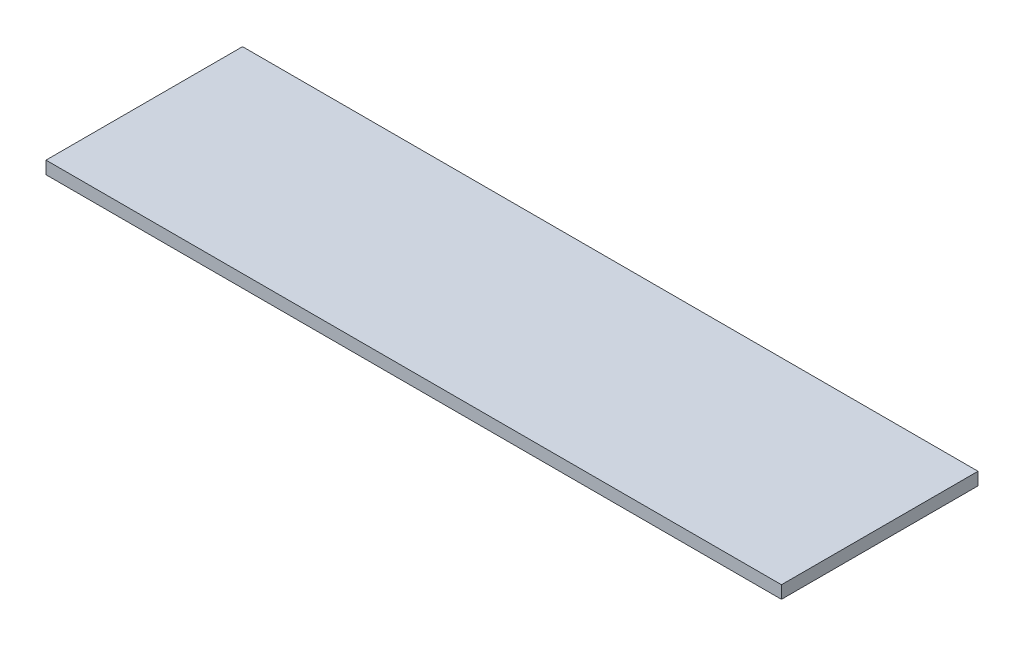
SolidWorks part; units mm, degrees
ref_plane "Plan de face" through (0, 0, 0) normal (0, 0, 1) x (1, 0, 0)
ref_plane "Plan de dessus" through (0, 0, 0) normal (0, 1, 0) x (1, 0, 0)
ref_plane "Plan de droite" through (0, 0, 0) normal (1, 0, 0) x (0, 0, -1)
sketch "Esquisse1" plane through (0, 0, 0) normal (0, 1, 0) x (1, 0, 0)
  line L1 (0, 0) -> (580, 0)
  line L2 (0, 0) -> (0, 155)
  line L3 (0, 155) -> (580, 155)
  line L4 (580, 0) -> (580, 155)
  dimension "D1" = 580
  dimension "D2" = 155
extrude "Boss.-Extru.1" add sketch "Esquisse1" along normal blind 10
